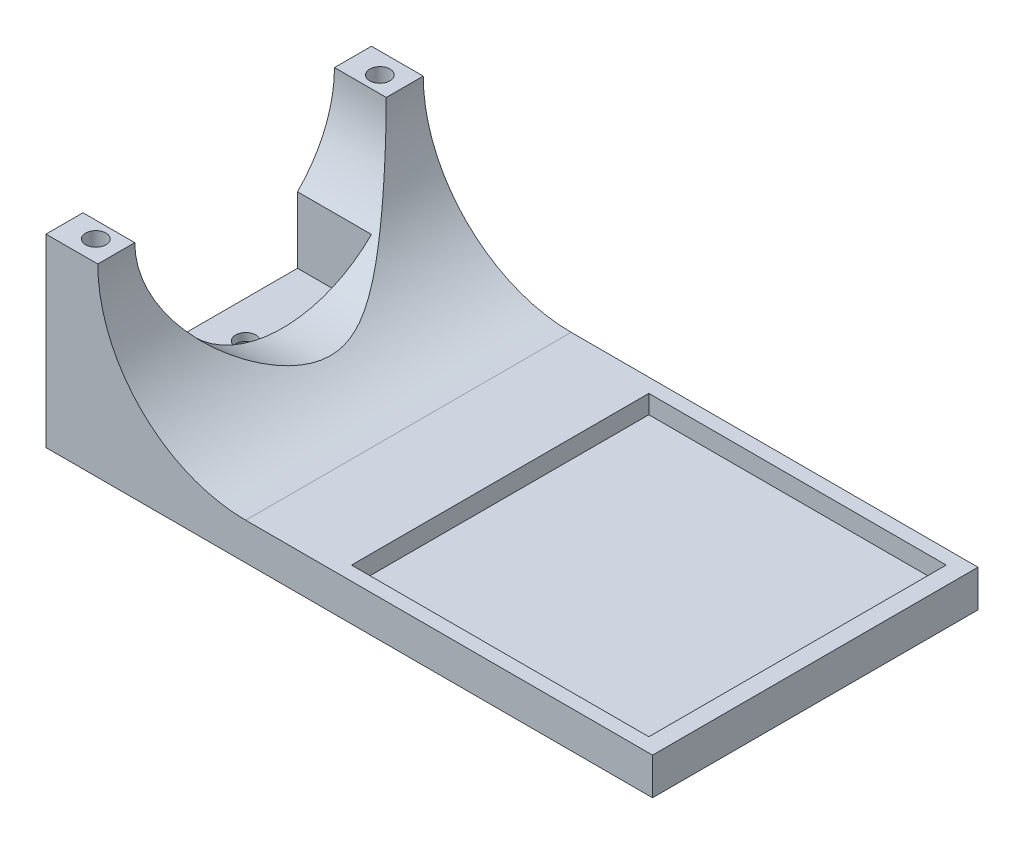
SolidWorks part; units mm, degrees
ref_plane "Front Plane" through (0, 0, 0) normal (0, 0, 1) x (1, 0, 0)
ref_plane "Top Plane" through (0, 0, 0) normal (0, 1, 0) x (1, 0, 0)
ref_plane "Right Plane" through (0, 0, 0) normal (1, 0, 0) x (0, 0, -1)
sketch "Sketch2" plane through (0, 0, 0) normal (0, 1, 0) x (1, 0, 0)
  line L4 (451.104, -14.859) -> (348.996, -14.859)
  line L5 (451.104, -14.859) -> (451.104, 87.249)
  line L6 (451.104, 87.249) -> (348.996, 87.249)
  line L7 (348.996, -14.859) -> (348.996, 87.249)
  line L8 (457.2, -19.685) -> (-50.8, -19.685)
  line L9 (457.2, -19.685) -> (457.2, 92.075)
  line L10 (457.2, 92.075) -> (-50.8, 92.075)
  line L11 (-50.8, -19.685) -> (-50.8, 92.075)
  line L12 (436.88, -0.635) -> (304.8, -0.635)
  line L13 (436.88, -0.635) -> (436.88, 89.789)
  line L14 (436.88, 89.789) -> (304.8, 89.789)
  line L15 (304.8, -0.635) -> (304.8, 89.789)
  line L16 (433.07, 3.175) -> (313.563, 3.175)
  line L17 (433.07, 3.175) -> (433.07, 85.979)
  line L18 (433.07, 85.979) -> (313.563, 85.979)
  line L19 (313.563, 3.175) -> (313.563, 85.979)
  line L20 (313.563, 48.895) -> (301.244, 48.895)
  line L21 (313.563, 48.895) -> (313.563, 77.089)
  line L22 (313.563, 77.089) -> (301.244, 77.089)
  line L23 (301.244, 48.895) -> (301.244, 77.089)
  line L24 (301.244, 68.453) -> (294.64, 68.453)
  line L25 (301.244, 68.453) -> (301.244, 77.089)
  line L26 (301.244, 77.089) -> (294.64, 77.089)
  line L27 (294.64, 68.453) -> (294.64, 77.089)
  line L28 (203.2, 92.075) -> (203.2, -19.685)
  line L33 (203.2, 48.895) -> (177.8, 61.595)
  line L34 (177.8, 61.595) -> (177.8, 10.795)
  line L35 (177.8, 10.795) -> (203.2, 23.495)
  circle A0 centre (400.05, 36.195) radius 20.32
  circle A1 centre (400.05, 36.195) radius 29.21
  dimension "D1" = 40.64
  dimension "D2" = 58.42
  dimension "D3" = 82.804
  dimension "D4" = 90.424
  dimension "D5" = 132.08
  dimension "D6" = 119.507
  dimension "D7" = 3.81
  dimension "D8" = 3.81
  dimension "D9" = 28.194
  dimension "D10" = 8.636
  dimension "D11" = 12.319
  dimension "D12" = 508
  dimension "D13" = 33.02
  dimension "D14" = 33.02
  dimension "D15" = 111.76
  dimension "D16" = 102.108
  dimension "D17" = 57.15
  dimension "D18" = 51.054
  dimension "D19" = 102.108
  dimension "D20" = 51.054
  dimension "D21" = 50.8
  dimension "D22" = 8.89
  dimension "D23" = 55.88
  dimension "D24" = 12.7
  dimension "D25" = 25.4
  dimension "D26" = 12.7
  dimension "D27" = 25.4
sketch "Sketch3" plane through (0, 0, 0) normal (0, 1, 0) x (1, 0, 0)
  line L1 (-50.8, 92.075) -> (457.2, 92.075)
  line L2 (-50.8, 92.075) -> (-50.8, -19.685)
  line L3 (-50.8, -19.685) -> (457.2, -19.685)
  line L4 (457.2, 92.075) -> (457.2, -19.685)
extrude "Boss-Extrude1" add sketch "Sketch3" along normal blind 63.5
extrude "Cut-Extrude1" cut sketch "Sketch2" along normal blind 111.76 from offset 6.35 contours L6 L7 L4 L5
sketch "Sketch4" plane through (0, 0, 19.685) normal (0, 0, 1) x (1, 0, 0)
  line L0 (457.2, 0) -> (241.3, 0)
  line L1 (-50.8, 0) -> (457.2, 0) construction
  line L2 (457.2, 12.7) -> (317.5, 12.7)
  line L4 (457.2, 63.5) -> (457.2, 0) construction
  line L5 (317.5, 12.7) -> (266.7, 63.5)
  line L7 (457.2, 12.7) -> (457.2, 63.5)
  line L8 (266.7, 63.5) -> (457.2, 63.5)
  circle A0 centre (317.5, 63.5) radius 50.8
  line M3 (457.2, 0) -> (457.2, 63.5)
  line M4 (457.2, 63.5) -> (-50.8, 63.5)
  dimension "D1" = 215.9
  dimension "D2" = 139.7
  dimension "D3" = 12.7
  dimension "D4" = 135
  dimension "D5" = 50.8
extrude "Cut-Extrude2" cut sketch "Sketch4" against normal blind 156.718 contours L8 L5 L7 M4 | L5 L2 M3 M4 | L8 A0 L5 M4 | L5 A0 | A0 region at (406.655, 36.5649, 19.685) region at (287.8338, 33.8338, 19.685) region at (324.0868, 43.7396, 19.685) region at (317.5, 85.0602, 19.685)
sketch "Sketch5" plane through (0, 0, 0) normal (1, 0, 0) x (0, 0, -1)
  line L1 (92.075, 63.5) -> (-19.685, 63.5) construction
  circle A0 centre (36.195, 63.5) radius 43.18
  dimension "D1" = 86.36
extrude "Cut-Extrude3" cut sketch "Sketch5" along normal blind 355.6 contours A0
sketch "Sketch6" plane through (0, 63.5, 0) normal (0, 1, 0) x (1, 0, 0)
  line L0 (457.2, -19.685) -> (-50.8, -19.685) construction
  line L1 (-45.72, -14.605) -> (220.98, -14.605)
  line L2 (-45.72, -14.605) -> (-45.72, 86.995)
  line L3 (-45.72, 86.995) -> (220.98, 86.995)
  line L4 (220.98, -14.605) -> (220.98, 86.995)
  line L5 (-50.8, -19.685) -> (-50.8, 92.075) construction
  dimension "D1" = 101.6
  dimension "D2" = 5.08
  dimension "D3" = 5.08
  dimension "D4" = 266.7
extrude "Cut-Extrude4" cut sketch "Sketch6" against normal blind 50.8
sketch "Sketch7" plane through (0, 63.5, 0) normal (0, 1, 0) x (1, 0, 0)
  line L0 (237.5414, -13.805) -> (229.8186, -13.805)
  line L1 (223.68, 36.195) -> (243.68, 36.195)
  line L2 (233.68, 36.195) -> (233.68, -13.805)
  line L3 (-45.72, 36.195) -> (169.3056, 36.195)
  line L4 (-45.72, 86.995) -> (-45.72, -14.605) construction
  arc A0 (229.8186, -13.805) -> (223.68, 36.195) centre (430.38, 36.195) cw
  arc A1 (237.5414, -13.805) -> (243.68, 36.195) centre (36.98, 36.195) ccw
  dimension "D1" = 279.4
revolve "Cut-Revolve1" cut sketch "Sketch7" angle 360 about L3 region at (236.0376, 63.5, 10.203) region at (238.0319, 63.5, -16.5343)
sketch "Sketch8" plane through (0, 0, 0) normal (0, -1, 0) x (1, 0, 0)
  line L0 (248.92, 19.685) -> (248.92, -5.715)
  line L1 (457.2, 19.685) -> (-50.8, 19.685) construction
  line L2 (457.2, -92.075) -> (-50.8, -92.075) construction
  line L3 (248.92, -66.675) -> (274.32, -66.675)
  line L4 (274.32, -66.675) -> (274.32, -5.715)
  line L5 (274.32, -5.715) -> (248.92, -5.715)
  line L6 (-50.8, 19.685) -> (-50.8, -92.075) construction
  line L7 (248.92, 19.685) -> (493.4487, 67.9966)
  line L8 (493.4487, 67.9966) -> (493.4487, -149.5564)
  line L9 (493.4487, -149.5564) -> (248.92, -92.075)
  line L10 (248.92, -66.675) -> (248.92, -92.075)
  dimension "D1" = 299.72
  dimension "D2" = 25.4
  dimension "D3" = 25.4
  dimension "D4" = 25.4
extrude "Cut-Extrude5" cut sketch "Sketch8" against normal blind 174.244 flip side to cut contours L9 L10 L3 L4 L5 L0 L7 L8
sketch "Sketch9" plane through (0, 0, 0) normal (0, -1, 0) x (1, 0, 0)
  line L0 (266.7, -92.075) -> (317.5, -92.075) construction
  line L1 (274.32, -5.715) -> (248.92, -5.715)
  line L2 (274.32, -5.715) -> (274.32, -66.675)
  line L3 (274.32, -66.675) -> (248.92, -66.675)
  line L4 (248.92, -5.715) -> (248.92, -66.675)
  line L5 (317.5, 19.685) -> (266.7, 19.685) construction
  line L6 (248.92, -66.675) -> (248.92, -79.375) construction
  point P12 (248.92, -73.025)
  dimension "D1" = 25.4
  dimension "D2" = 25.4
  dimension "D3" = 25.4
extrude "Boss-Extrude2" add sketch "Sketch9" against normal blind 10.16
sketch "Sketch10" plane through (0, 0, 0) normal (0, -1, 0) x (1, 0, 0)
  line L0 (248.92, 19.685) -> (248.92, -92.075) construction
  line L1 (248.92, 19.685) -> (457.2, 19.685) construction
  line L2 (457.2, -92.075) -> (248.92, -92.075) construction
  circle A0 centre (258.9149, -84.963) radius 3.5
  circle A1 centre (258.9149, 12.573) radius 3.5
  circle A2 centre (258.9149, 12.573) radius 5.5
  circle A3 centre (258.9149, -84.963) radius 5.5
  dimension "D4" = 7
  dimension "D5" = 7
  dimension "D7" = 11
  dimension "D8" = 11
  dimension "D1" = 9.9949
  dimension "D2" = 9.9949
  dimension "D3" = 7.112
  dimension "D6" = 7.112
extrude "Cut-Extrude6" cut sketch "Sketch10" against normal blind 93.98 contours A1 | A0
extrude "Cut-Extrude7" cut sketch "Sketch10<3>" against normal blind 45.72 contours A2 | A3
sketch "Sketch10<3>" plane through (0, 0, 0) normal (0, -1, 0) x (1, 0, 0) same geometry as "Sketch10"
sketch "Sketch12" plane through (0, 0, 0) normal (0, -1, 0) x (1, 0, 0)
  line L0 (248.92, 19.685) -> (248.92, -92.075) construction
  line L1 (248.92, 19.685) -> (457.2, 19.685) construction
  circle A0 centre (261.62, -36.195) radius 5.5
  circle A1 centre (261.62, -36.195) radius 3.5
  dimension "D1" = 11
  dimension "D2" = 7
  dimension "D3" = 12.7
  dimension "D4" = 55.88
extrude "Cut-Extrude8" cut sketch "Sketch12" against normal blind 93.98 contours A1
extrude "Cut-Extrude9" cut sketch "Sketch12<3>" against normal blind 7.5 contours A0
sketch "Sketch12<3>" plane through (0, 0, 0) normal (0, -1, 0) x (1, 0, 0) same geometry as "Sketch12"
